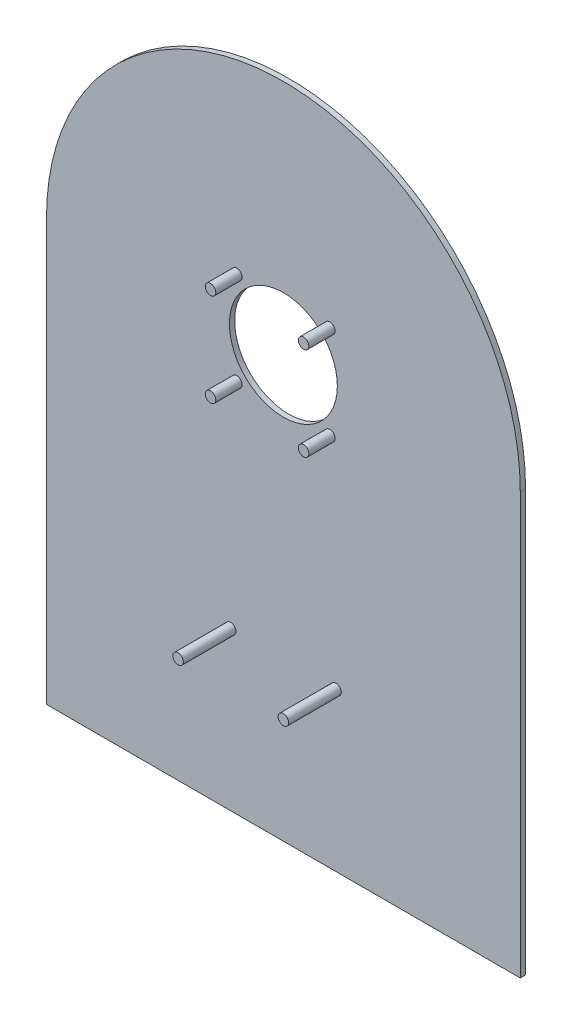
SolidWorks part; units mm, degrees
ref_plane "Face" through (0, 0, 0) normal (0, 0, 1) x (1, 0, 0)
ref_plane "Dessus" through (0, 0, 0) normal (0, 1, 0) x (1, 0, 0)
ref_plane "Droite" through (0, 0, 0) normal (1, 0, 0) x (0, 0, -1)
sketch "Esquisse1" plane through (0, 0, 0) normal (0, 0, 1) x (1, 0, 0)
  line L0 (-90, -160) -> (90, -160)
  line L1 (90, 0) -> (90, -160)
  line L2 (-90, 0) -> (-90, -160)
  arc A0 (90, 0) -> (-90, 0) centre (0, 0) ccw
  circle A1 centre (0, 0) radius 20.5
  dimension "D1" = 180
  dimension "D3" = 41
  dimension "D2" = 160
extrude "Boss.-Extru.1" add sketch "Esquisse1" along normal blind 2
ref_axis "Axe3" through (0, 0, -80.9) along (0, 0, 1)
sketch "Esquisse2" plane through (0, 0, 2) normal (0, 0, 1) x (1, 0, 0)
  line L0 (17.6777, 17.6777) -> (0, 0) construction
  line L1 (0, 0) -> (20.5, 0) construction
  line L2 (0, 0) -> (-17.6777, -17.6777) construction
  line L3 (-17.6777, 17.6777) -> (0, 0) construction
  line L4 (0, 0) -> (17.6777, -17.6777) construction
  circle A0 centre (0, 0) radius 25 construction
  circle A1 centre (0, 0) radius 20.5 construction
  circle A2 centre (-17.6777, 17.6777) radius 2
  circle A3 centre (17.6777, 17.6777) radius 2
  circle A4 centre (17.6777, -17.6777) radius 2
  circle A5 centre (-17.6777, -17.6777) radius 2
  dimension "D1" = 50
  dimension "D2" = 45
  dimension "D3" = 90
extrude "Goujon M4x10" add sketch "Esquisse2" along normal blind 10
sketch "Esquisse3" plane through (0, 0, 2) normal (0, 0, 1) x (1, 0, 0)
  line L0 (-90, -160) -> (90, -160) construction
  circle A0 centre (-20, -100) radius 2
  circle A1 centre (0, 0) radius 20.5 construction
  circle A2 centre (20, -100) radius 2
  dimension "D1" = 60
  dimension "D2" = 20
  dimension "D3" = 40
  dimension "D4" = 60
extrude "Goujon M4x20" add sketch "Esquisse3" along normal blind 20
